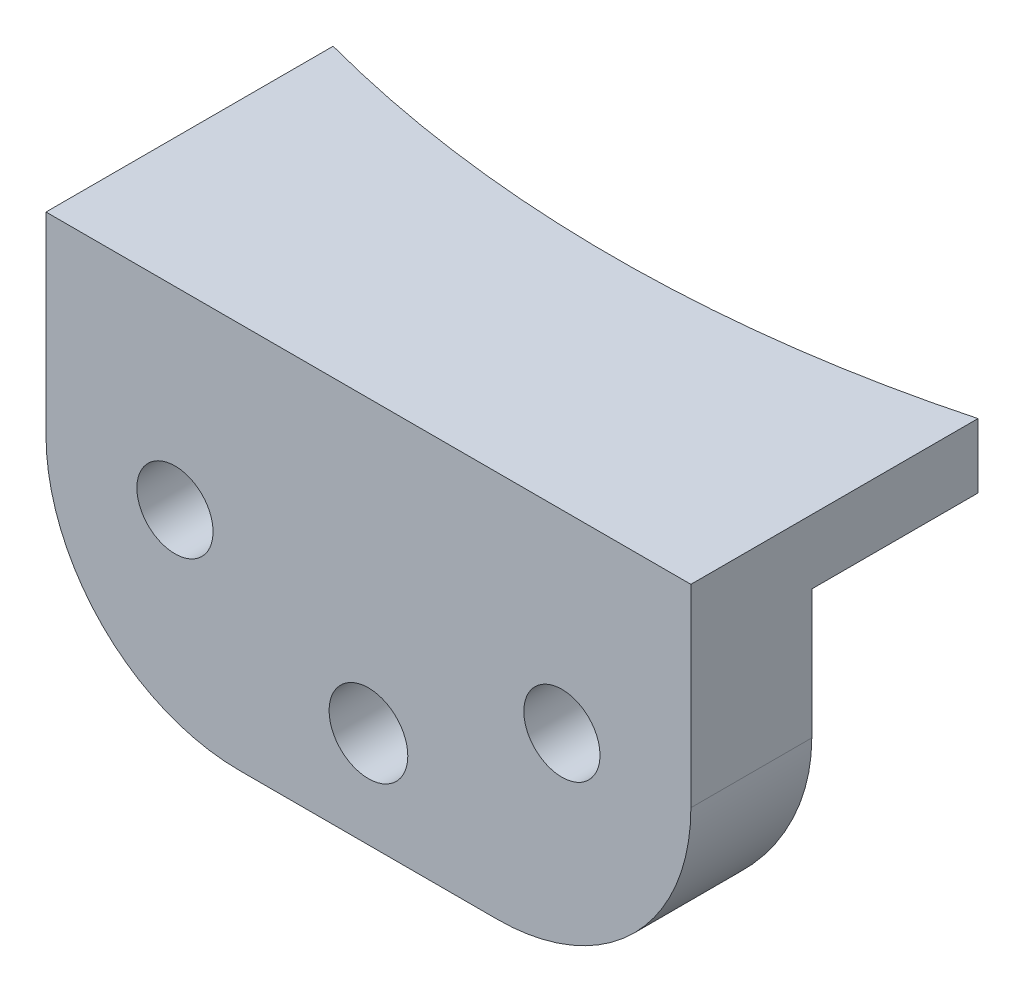
SolidWorks part; units mm, degrees
note: The reader was unsure of these and kept them because the rebuilt part matched: shared geometry of "Sketch2<4>".
material "6061 Alloy"
ref_plane "Front Plane" through (0, 0, 0) normal (0, 0, 1) x (1, 0, 0)
ref_plane "Top Plane" through (0, 0, 0) normal (0, 1, 0) x (1, 0, 0)
ref_plane "Right Plane" through (0, 0, 0) normal (1, 0, 0) x (0, 0, -1)
sketch "Sketch1" plane through (0, 0, 0) normal (0, 1, 0) x (1, 0, 0)
  line L0 (-12.7, -54.0916) -> (-12.7, -57.3481)
  line L1 (12.7, -54.0916) -> (12.7, -57.3481)
  line L2 (-12.7, -58.8541) -> (12.7, -58.8541)
  line L3 (-12.7, -57.3481) -> (-12.7, -58.8541)
  line L4 (12.7, -57.3481) -> (12.7, -58.8541)
  line L5 (0, -58.7375) -> (21.9276, -58.7375)
  circle A0 centre (0, 0) radius 55.5625
  circle A1 centre (0, 0) radius 58.7375
  dimension "D1" = 111.125
  dimension "D3" = 12.7
  dimension "D4" = 12.7
  dimension "D5" = 4.7625
  dimension "D6" = 0.1166
  dimension "D2" = 3.175
extrude "Boss-Extrude1" add sketch "Sketch1" along normal blind 12.7 contours L0 A1 L1 A0 | A1 L3 L2 | A1 L2 L4
sketch "Sketch2" plane through (0, 0, 0) normal (0, 0, 1) x (1, 0, 0)
  line L0 (0, 12.7) -> (0, 0) construction
  line L5 (-12.7, 0) -> (12.7, 0)
  line L6 (12.7, 0) -> (12.7, 12.7)
  line L7 (12.7, 12.7) -> (-12.7, 12.7)
  line L12 (-12.7, 12.7) -> (-12.7, 0)
  line L13 (-12.7, 0) -> (12.7, 0)
  line L14 (12.7, 0) -> (12.7, 12.7)
  line L15 (12.7, 12.7) -> (-12.7, 12.7)
  line L16 (-12.7, 12.7) -> (-12.7, 0)
  circle A0 centre (-7.62, 7.62) radius 1.5
  circle A1 centre (0, 3.81) radius 1.55
  dimension "D6" = 3
  dimension "D4" = 3.1
  dimension "D5" = 7.62
  dimension "D2" = 7.62
  dimension "D3" = 3.81
  dimension "D7" = 3.81
extrude "Cut-Extrude1" cut sketch "Sketch2" along normal up to surface (58.8541 mm away) contours A0 up to face at (0, 6.35, 58.8541)
mirror "Mirror1" about plane through (0, 0, 0) normal (1, 0, 0) of "Cut-Extrude1"
fillet "Fillet1" radius 7.62 2 edges at (-12.7, 0, 56.4729) (12.7, 0, 56.4729)
extrude "Cut-Extrude2" cut sketch "Sketch2<4>" along normal through all contours A1 L0 | L0 A1
sketch "Sketch2<4>" plane through (0, 0, 0) normal (0, 0, 1) x (1, 0, 0) same geometry as "Sketch2"
sketch "Sketch7" plane through (0, 12.7, 0) normal (0, 1, 0) x (1, 0, 0)
  line L3 (-12.7, -58.8541) -> (12.7, -58.8541)
  line L4 (12.7, -58.8541) -> (12.7, -54.0916)
  line L5 (-12.7, -54.0916) -> (-12.7, -58.8541)
  line L6 (-12.7, -58.8541) -> (12.7, -58.8541)
  line L7 (12.7, -58.8541) -> (12.7, -54.0916)
  line L8 (-12.7, -54.0916) -> (-12.7, -58.8541)
  line L9 (-12.7, -54.0916) -> (-12.7, -47.5456)
  line L10 (12.7, -54.0916) -> (12.7, -47.5456)
  line L11 (-12.7, -58.8541) -> (-12.7, -47.5456)
  line L12 (-19.05, -45.3758) -> (-19.05, -65.2041) construction
  line L13 (-19.05, -65.2041) -> (19.05, -65.2041) construction
  line L14 (19.05, -65.2041) -> (19.05, -45.3758) construction
  line L15 (12.7, -47.5456) -> (12.7, -58.8541)
  line L16 (-12.7, -58.8541) -> (12.7, -58.8541)
  arc A0 (-12.7, -47.5456) -> (12.7, -47.5456) centre (0, 0) ccw
  arc A1 (-12.7, -54.0916) -> (12.7, -54.0916) centre (0, 0) ccw
  arc A2 (-12.7, -54.0916) -> (12.7, -54.0916) centre (0, 0) ccw
  arc A3 (-19.05, -45.3758) -> (19.05, -45.3758) centre (0, 0) ccw construction
  line M11 (-12.7, -58.8541) -> (12.7, -58.8541)
  line M12 (12.7, -58.8541) -> (12.7, -54.0916)
  arc M13 (12.7, -54.0916) -> (-12.7, -54.0916) centre (0, 0) cw
  line M14 (-12.7, -54.0916) -> (-12.7, -58.8541)
  dimension "D1" = 0
  dimension "D2" = 6.35
extrude "Boss-Extrude2" add sketch "Sketch7" along normal blind 2.54 contours M14 M11 M12 M13 | A0 L9 L10 M13
equation "\"Middle Coupler Inner Daimeter\"= 3.875in"
equation "\"Middle Coupler  Wall Thickness\" = 0.25in"
equation "\"Middle Coupler Bottom Thickness\"= 0.2in"
equation "\"Bearing Rail Offset\"= 0.45in"
equation "\"3-56 UNF Tap\"= 0.089in"
equation "\"3-56 UNF Clearance\"= 0.104in"
equation "\"Ball Bearing Distance\"= 0.03in"
equation "\"TCA Outer Diameter\" = 6in"
equation "\"D1@Sketch1\"=\"Middle Coupler Inner Daimeter\"+0.5"
equation "\"D2@Sketch1\"=1/8"
equation "\"D3@Sketch1\"=0.5"
equation "\"D4@Sketch1\"=\"D3@Sketch1\""
equation "\"D6@Sketch2\"=3mm"
equation "\"Interstage Aeroframe Wall Thickness\" = 0.072in"
equation "\"Compression Spring OD\"= 0.42in"
equation "\"10-24 Tap\"= 0.1495in"
equation "\"10-24 Clearance\"= 0.196in"
equation "\"Lower Stage Fuselage Wall Thickness\" = 0.25in"
equation "\"6-32 Tap\" = 0.107in"
equation "\"1/4-20 Tap\" = 0.201in"
equation "\"3-48 Tap\"= 0.079in"
equation "\"3-48 Clearance\" = 0.104in"
equation "\"6-32 Clearance\" = 0.144in"
equation "\"12-24 Tap\" = 0.177in"
equation "\"D5@Sketch1\"=3/16"
equation "\"4-40 Tap\"= 0.089in"
equation "\"4-40 Clearance\" = 0.116in"
equation "\"12-24 Major Diameter\"= 0.216in"
equation "\"D4@Sketch2\"=3.1mm"
